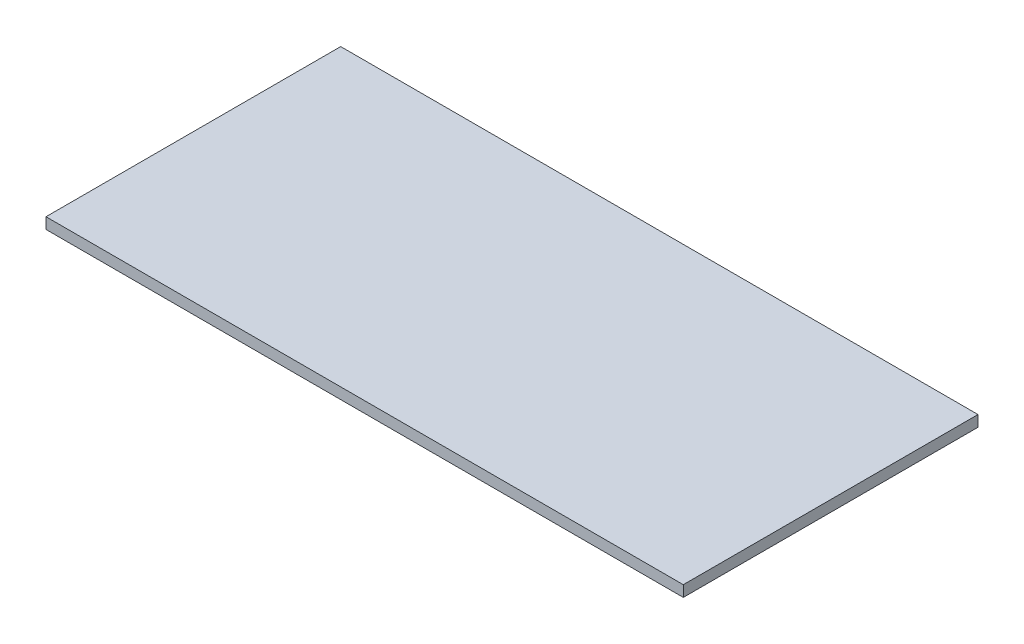
SolidWorks part; units mm, degrees
ref_plane "Front Plane" through (0, 0, 0) normal (0, 0, 1) x (1, 0, 0)
ref_plane "Top Plane" through (0, 0, 0) normal (0, 1, 0) x (1, 0, 0)
ref_plane "Right Plane" through (0, 0, 0) normal (1, 0, 0) x (0, 0, -1)
sketch "Sketch1" plane through (0, 0, 0) normal (0, 1, 0) x (1, 0, 0)
  line L1 (0, 0) -> (86.5, 0)
  line L2 (0, 0) -> (0, 40)
  line L3 (0, 40) -> (86.5, 40)
  line L4 (86.5, 0) -> (86.5, 40)
  dimension "D1" = 40
  dimension "D2" = 86.5
extrude "Boss-Extrude1" add sketch "Sketch1" along normal blind 1.5
